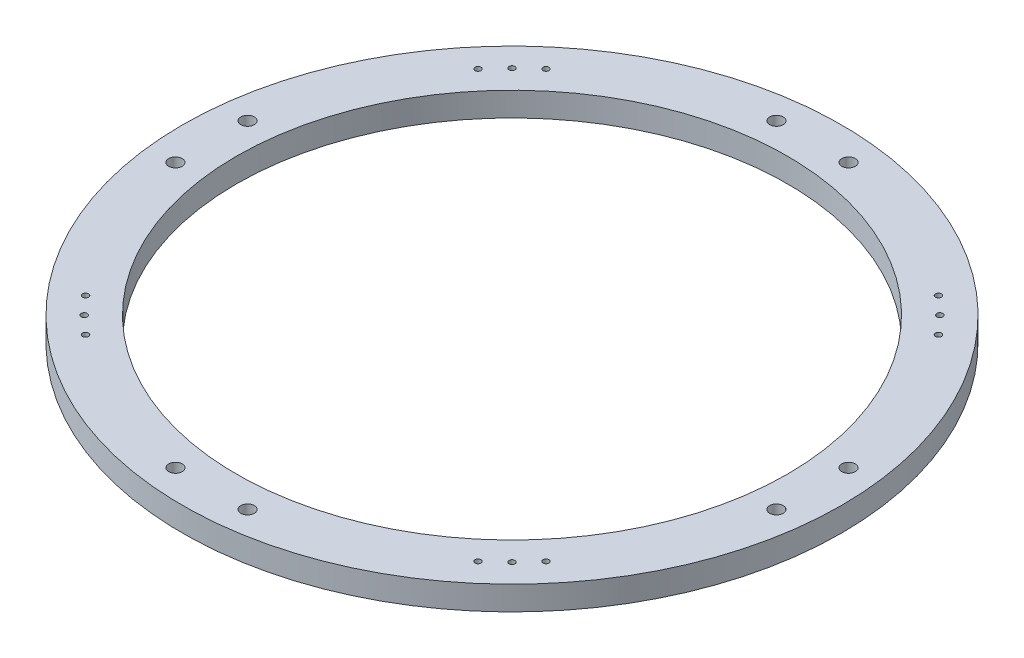
SolidWorks part; units mm, degrees
material "Oak"
ref_plane "Front Plane" through (0, 0, 0) normal (0, 0, 1) x (1, 0, 0)
ref_plane "Top Plane" through (0, 0, 0) normal (0, 1, 0) x (1, 0, 0)
ref_plane "Right Plane" through (0, 0, 0) normal (1, 0, 0) x (0, 0, -1)
sketch "Sketch1" plane through (0, 0, 0) normal (0, 0, 1) x (1, 0, 0)
  line L0 (0, -200000) -> (0, 218797.9879) construction
  line L5 (0, -200000) -> (0, 218797.9879) construction
  line L6 (174.1012, 207.3685) -> (174.1012, 194.6685)
  line L7 (145.5262, 207.3685) -> (174.1012, 207.3685)
  line L8 (174.1012, 194.6685) -> (145.5262, 194.6685)
  line L9 (145.5262, 194.6685) -> (145.5262, 207.3685)
revolve "Revolve1" add sketch "Sketch1" angle 360 about L5
hole_wizard "1/8 (0.125) Diameter Hole1" positions "Sketch5" profile "Sketch6" hole size "1/8" standard "ANSI Inch" end condition through all
sketch "Sketch5" plane through (0, 207.3685, 0) normal (0, 1, 0) x (1, 0, 0)
  point P0 (-113.0054, 113.0054)
  point P3 (-103.6677, 121.6282)
  point P6 (-121.6282, 103.6677)
sketch "Sketch6" plane through (-113.0054, 207.3685, -113.0054) normal (1, 0, 0) x (0, 0, 1)
  line L0 (0, 0) -> (0, 12.7)
  line L1 (0, 12.7) -> (1.5875, 12.7)
  line L2 (1.5875, 12.7) -> (1.5875, 0)
  line L5 (1.5875, 0) -> (0, 0)
  line L11 (0, -6.35) -> (0, 107.95) construction
  dimension "Thru Hole Dia." = 3.175
  dimension "Thru Hole Depth" = 12.7
sketch "Sketch7" plane through (0, 207.3685, 0) normal (0, 1, 0) x (1, 0, 0)
  line L0 (0, 0) -> (158.75, 0) construction
  line L1 (158.75, 19.05) -> (158.75, -19.05) construction
  circle A0 centre (158.75, -19.05) radius 3.5719
  circle A1 centre (158.75, 19.05) radius 3.5719
  point P6 (158.75, 0)
  dimension "D3" = 7.1437
  dimension "D1" = 38.1
  dimension "D2" = 158.75
extrude "Cut-Extrude1" cut sketch "Sketch7" against normal through all
pattern_circular "CirPattern1" count 4 over 360 about axis through (0, -200000, 0) along (0, -1, 0) of "1/8 (0.125) Diameter Hole1", "Cut-Extrude1"
